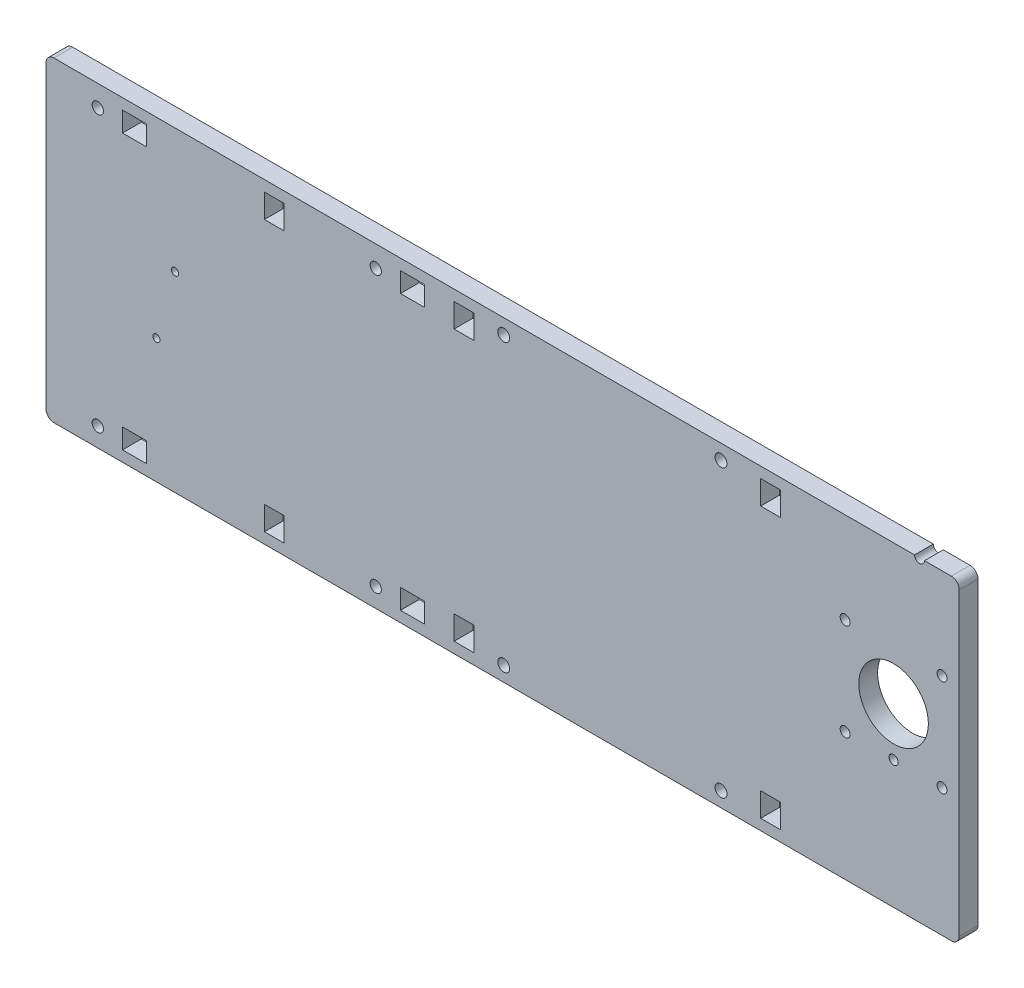
SolidWorks part; units mm, degrees
material "Acrylic (Medium-high impact)"
ref_plane "Front Plane" through (0, 0, 0) normal (0, 0, 1) x (1, 0, 0)
ref_plane "Top Plane" through (0, 0, 0) normal (0, 1, 0) x (1, 0, 0)
ref_plane "Right Plane" through (0, 0, 0) normal (1, 0, 0) x (0, 0, -1)
sketch "Sketch1" plane through (0, 0, 0) normal (0, 0, 1) x (1, 0, 0)
  line L1 (0, 0) -> (292.1, 0)
  line L2 (0, 0) -> (0, 101.0158)
  line L3 (0, 101.0158) -> (292.1, 101.0158)
  line L4 (292.1, 0) -> (292.1, 101.0158)
  line L5 (234.95, 97.5614) -> (228.6, 97.5614)
  line L6 (234.95, 97.5614) -> (234.95, 89.9414)
  line L7 (234.95, 89.9414) -> (228.6, 89.9414)
  line L8 (228.6, 97.5614) -> (228.6, 89.9414)
  line L9 (69.85, 97.5614) -> (76.2, 97.5614)
  line L10 (69.85, 97.5614) -> (69.85, 89.9414)
  line L11 (69.85, 89.9414) -> (76.2, 89.9414)
  line L12 (76.2, 97.5614) -> (76.2, 89.9414)
  line L13 (234.95, 3.4544) -> (228.6, 3.4544)
  line L14 (234.95, 3.4544) -> (234.95, 11.0744)
  line L15 (234.95, 11.0744) -> (228.6, 11.0744)
  line L16 (228.6, 3.4544) -> (228.6, 11.0744)
  line L17 (76.2, 3.4544) -> (69.85, 3.4544)
  line L18 (76.2, 3.4544) -> (76.2, 11.0744)
  line L19 (76.2, 11.0744) -> (69.85, 11.0744)
  line L20 (69.85, 3.4544) -> (69.85, 11.0744)
  dimension "D1" = 292.1
  dimension "D2" = 3.4544
  dimension "D3" = 7.62
  dimension "D4" = 6.35
  dimension "D5" = 57.15
  dimension "D6" = 165.1
  dimension "D7" = 3.4544
  dimension "D8" = 78.867
extrude "Boss-Extrude1" add sketch "Sketch1" along normal blind 6
sketch "Sketch2" plane through (0, 0, 6) normal (0, 0, 1) x (1, 0, 0)
  line L0 (0, 50.5079) -> (292.1, 50.5079) construction
  line L1 (0, 101.0158) -> (0, 0) construction
  line L2 (292.1, 0) -> (292.1, 101.0158) construction
  line L4 (255.6, 40.9261) -> (286.6, 40.9261) construction
  line L5 (255.6, 40.9261) -> (255.6, 71.9261) construction
  line L6 (255.6, 71.9261) -> (286.6, 71.9261) construction
  line L7 (286.6, 40.9261) -> (286.6, 71.9261) construction
  line L8 (255.6, 40.9261) -> (286.6, 71.9261) construction
  line L9 (255.6, 71.9261) -> (286.6, 40.9261) construction
  circle A0 centre (271.1, 56.4261) radius 11.125
  circle A1 centre (255.6, 71.9261) radius 1.5875
  circle A2 centre (255.6, 40.9261) radius 1.5875
  circle A3 centre (286.6, 40.9261) radius 1.5875
  circle A4 centre (286.6, 71.9261) radius 1.5875
  circle A5 centre (271.1, 40.9261) radius 1.4605
  point P6 (271.1, 56.4261)
  dimension "D4" = 3.175
  dimension "D5" = 22.25
  dimension "D6" = 2.921
  dimension "D1" = 5.9182
  dimension "D2" = 21
  dimension "D3" = 31
extrude "Cut-Extrude1" cut sketch "Sketch2" against normal through all
sketch "Sketch3" plane through (0, 0, 6) normal (0, 0, 1) x (1, 0, 0)
  line L0 (121, 3.4544) -> (113.38, 3.4544) construction
  line L1 (121, 97.5614) -> (113.38, 97.5614)
  line L2 (121, 97.5614) -> (121, 91.5614)
  line L3 (121, 91.5614) -> (113.38, 91.5614)
  line L4 (113.38, 97.5614) -> (113.38, 91.5614)
  line L5 (121, 9.4544) -> (113.38, 9.4544)
  line L6 (121, 9.4544) -> (121, 3.4544)
  line L7 (121, 3.4544) -> (113.38, 3.4544)
  line L8 (113.38, 9.4544) -> (113.38, 3.4544)
  line L9 (32.1, 3.4544) -> (113.38, 3.4544) construction
  line L11 (24.48, 9.4544) -> (32.1, 9.4544)
  line L12 (24.48, 9.4544) -> (24.48, 3.4544)
  line L13 (24.48, 3.4544) -> (32.1, 3.4544)
  line L14 (32.1, 9.4544) -> (32.1, 3.4544)
  line L15 (24.48, 97.5614) -> (32.1, 97.5614)
  line L16 (24.48, 97.5614) -> (24.48, 91.5614)
  line L17 (24.48, 91.5614) -> (32.1, 91.5614)
  line L18 (32.1, 97.5614) -> (32.1, 91.5614)
extrude "Cut-Extrude2" cut sketch "Sketch3" against normal through all
sketch "Sketch4" plane through (0, 0, 6) normal (0, 0, 1) x (1, 0, 0)
  line L0 (32.1, 97.5614) -> (24.48, 97.5614) construction
  line L1 (24.48, 91.5614) -> (32.1, 91.5614)
  line L2 (24.48, 91.5614) -> (24.48, 91.2114)
  line L3 (24.48, 91.2114) -> (32.1, 91.2114)
  line L4 (32.1, 91.5614) -> (32.1, 91.2114)
  line L5 (24.48, 9.4544) -> (32.1, 9.4544)
  line L6 (24.48, 9.4544) -> (24.48, 9.8044)
  line L7 (24.48, 9.8044) -> (32.1, 9.8044)
  line L8 (32.1, 9.4544) -> (32.1, 9.8044)
  line L9 (113.38, 9.4544) -> (121, 9.4544)
  line L10 (113.38, 9.4544) -> (113.38, 9.8044)
  line L11 (113.38, 9.8044) -> (121, 9.8044)
  line L12 (121, 9.4544) -> (121, 9.8044)
  line L13 (113.38, 91.5614) -> (121, 91.5614)
  line L14 (113.38, 91.5614) -> (113.38, 91.2114)
  line L15 (113.38, 91.2114) -> (121, 91.2114)
  line L16 (121, 91.5614) -> (121, 91.2114)
  dimension "D1" = 6.35
extrude "Cut-Extrude3" cut sketch "Sketch4" against normal up to surface (6 mm away) up to face at (28.29, 94.5614, 0)
fillet "Fillet1" radius 2.54 4 edges at (292.1, 0, 3) (0, 0, 3) (292.1, 101.0158, 3) (0, 101.0158, 3)
sketch "Sketch5" plane through (0, 0, 6) normal (0, 0, 1) x (1, 0, 0)
  line L0 (81.438, 65.0009) -> (25.4246, 65.0009) construction
  line L1 (81.438, 61.1909) -> (41.275, 61.1909) construction
  line L2 (44.45, 83.4887) -> (44.45, 36.0149) construction
  line L3 (44.45, 36.0149) -> (25.4246, 36.0149) construction
  line L4 (25.4246, 36.0149) -> (25.4246, 0) construction
  line L5 (2.54, 0) -> (289.56, 0) construction
  line L6 (25.4246, 65.0009) -> (25.4246, 101.0158) construction
  line L7 (289.56, 101.0158) -> (2.54, 101.0158) construction
  line L8 (25.4246, 39.8249) -> (81.438, 39.8249) construction
  circle A0 centre (174.1545, 76.0009) radius 11 construction
  circle A1 centre (35.306, 39.8249) radius 1.143
  circle A2 centre (41.275, 61.1909) radius 1.143
  dimension "D5" = 2.286
  dimension "D1" = 3.81
  dimension "D2" = 3.175
  dimension "D3" = 21.3661
  dimension "D4" = 3.81
  dimension "D6" = 5.969
extrude "Cut-Extrude4" cut sketch "Sketch5" against normal through all
sketch "Sketch6" plane through (0, 0, 6) normal (0, 0, 1) x (1, 0, 0)
  line L0 (289.56, 101.0158) -> (2.54, 101.0158) construction
  line L1 (146.4, 96.2533) -> (215.9, 96.2533) construction
  line L2 (146.4, 96.2533) -> (146.4, 4.7625) construction
  line L3 (146.4, 4.7625) -> (215.9, 4.7625) construction
  line L4 (215.9, 96.2533) -> (215.9, 4.7625) construction
  line L5 (121, 91.2114) -> (121, 97.5614) construction
  line L6 (2.54, 0) -> (289.56, 0) construction
  line L7 (76.2, 97.5614) -> (69.85, 97.5614) construction
  line L8 (228.6, 97.5614) -> (228.6, 89.9414) construction
  line L9 (130.525, 97.5614) -> (136.875, 97.5614)
  line L10 (130.525, 97.5614) -> (130.525, 89.9414)
  line L11 (130.525, 89.9414) -> (136.875, 89.9414)
  line L12 (136.875, 97.5614) -> (136.875, 89.9414)
  line L13 (130.525, 3.4544) -> (136.875, 3.4544)
  line L14 (130.525, 3.4544) -> (130.525, 11.0744)
  line L15 (130.525, 11.0744) -> (136.875, 11.0744)
  line L16 (136.875, 3.4544) -> (136.875, 11.0744)
  line L17 (69.85, 89.9414) -> (76.2, 89.9414) construction
  line L18 (69.85, 3.4544) -> (76.2, 3.4544) construction
  circle A0 centre (146.4, 96.2533) radius 1.905
  circle A1 centre (215.9, 96.2533) radius 1.905
  circle A2 centre (215.9, 4.7625) radius 1.905
  circle A3 centre (146.4, 4.7625) radius 1.905
  dimension "D1" = 3.81
  dimension "D2" = 4.7625
  dimension "D3" = 4.7625
  dimension "D4" = 25.4
  dimension "D5" = 12.7
  dimension "D6" = 9.525
extrude "Cut-Extrude5" cut sketch "Sketch6" against normal through all
sketch "Sketch7" plane through (0, 0, 6) normal (0, 0, 1) x (1, 0, 0)
  line L0 (15.0058, 94.2114) -> (18.13, 94.2114) construction
  line L1 (103.9058, 94.2114) -> (107.03, 94.2114) construction
  line L2 (103.9058, 6.1044) -> (107.03, 6.1044) construction
  line L3 (15.0058, 6.1044) -> (18.13, 6.1044) construction
  circle A0 centre (16.5679, 94.2114) radius 1.8034
  circle A1 centre (105.4679, 94.2114) radius 1.8034
  circle A2 centre (105.4679, 6.1044) radius 1.8034
  circle A3 centre (16.5679, 6.1044) radius 1.8034
  dimension "D1" = 3.6068
extrude "Cut-Extrude6" cut sketch "Sketch7" against normal through all
sketch "Sketch8" plane through (0, 0, 6) normal (0, 0, 1) x (1, 0, 0)
  line L0 (289.56, 101.0158) -> (2.54, 101.0158) construction
  line L1 (292.1, 2.54) -> (292.1, 98.4758) construction
  circle A0 centre (279.4, 101.0158) radius 1.5875
  dimension "D2" = 3.175
  dimension "D1" = 12.7
extrude "Cut-Extrude7" cut sketch "Sketch8" against normal through all
